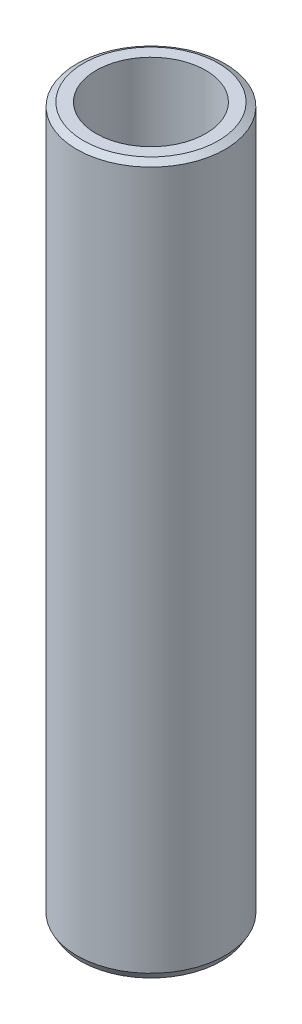
SolidWorks part; units mm, degrees
ref_plane "Front Plane" through (0, 0, 0) normal (0, 0, 1) x (1, 0, 0)
ref_plane "Top Plane" through (0, 0, 0) normal (0, 1, 0) x (1, 0, 0)
ref_plane "Right Plane" through (0, 0, 0) normal (1, 0, 0) x (0, 0, -1)
sketch "Sketch1" plane through (0, 0, 0) normal (0, 1, 0) x (1, 0, 0)
  circle A0 centre (0, 0) radius 50
  dimension "SHAFT_OD" = 100
extrude "Boss-Extrude1" add sketch "Sketch1" along normal blind 477.763
sketch "Sketch2" plane through (0, 0, 0) normal (0, 1, 0) x (1, 0, 0)
  circle A0 centre (0, 0) radius 36.9399
  dimension "BORE_D" = 73.8798
extrude "Cut-Extrude1" cut sketch "Sketch2" along normal through all
chamfer "Chamfer1" distance 2.6846 angle 60 2 edges at (0, 477.763, 50) (0, 0, 50) first distance on face at (0, 477.763, 50) first distance on face at (0, 0, 36.9399)
